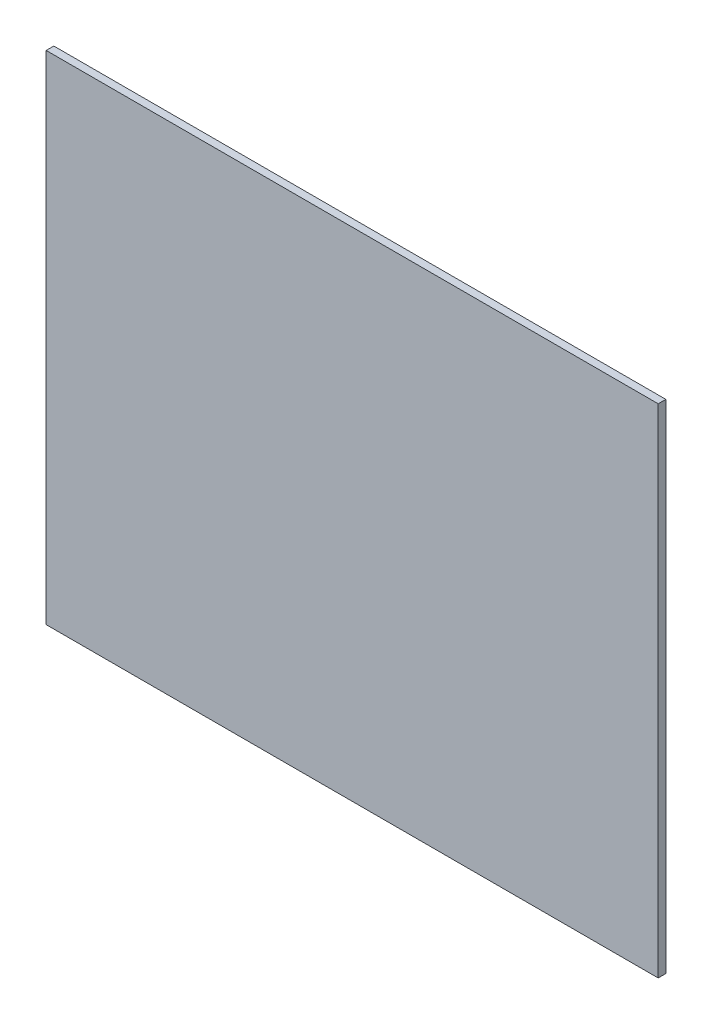
SolidWorks part; units mm, degrees
material "Akçaağaç"
ref_plane "Ön Düzlem" through (0, 0, 0) normal (0, 0, 1) x (1, 0, 0)
ref_plane "Üst Düzlem" through (0, 0, 0) normal (0, 1, 0) x (1, 0, 0)
ref_plane "Sağ Düzlem" through (0, 0, 0) normal (1, 0, 0) x (0, 0, -1)
sketch "Çizim1" plane through (0, 0, 0) normal (0, 0, 1) x (1, 0, 0)
  line L1 (400, -325) -> (-400, -325)
  line L2 (400, -325) -> (400, 325)
  line L3 (400, 325) -> (-400, 325)
  line L4 (-400, -325) -> (-400, 325)
  line L5 (400, -325) -> (-400, 325) construction
  line L6 (400, 325) -> (-400, -325) construction
  point P0 (0, 0)
  dimension "D1" = 650
  dimension "D2" = 800
base flange "Taban-Flanş1" sketch "Çizim1" thickness 10 reverse thickness direction no parameters "D1"=0.7366
sketch "Büküm-Çizgileri1" [suppressed] plane through (0, 0, 0) normal (0, 1, 0) x (1, 0, 0)
sketch "Sınırlandırma-Kutusu1" [suppressed] plane through (0, 0, 0) normal (0, 1, 0) x (1, 0, 0)
sheet metal parameters "Sac-Levha1" thickness 10 parameters "D1"=0.7366
flat pattern "Düz-Çoğaltma1" [suppressed]
sketch "Büküm-Çizgileri2" plane through (0, 0, 0) normal (0, 1, 0) x (1, 0, 0)
sketch3d "Sınırlandırma-Kutusu2" [suppressed]
  line L0 (-400, -325, 0) -> (400, -325, 0) construction
  line L1 (-400, 325, 0) -> (400, 325, 0) construction
  line L2 (-400, -325, 0) -> (-400, 325, 0) construction
  line L3 (400, -325, 0) -> (400, 325, 0) construction
